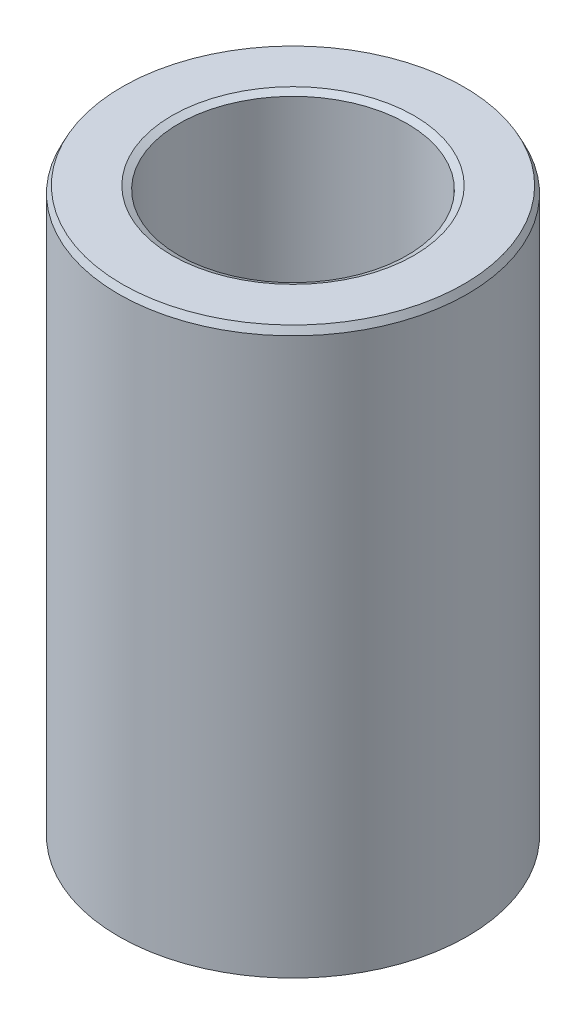
SolidWorks part; units mm, degrees
ref_plane "Front Plane" through (0, 0, 0) normal (0, 0, 1) x (1, 0, 0)
ref_plane "Top Plane" through (0, 0, 0) normal (0, 1, 0) x (1, 0, 0)
ref_plane "Right Plane" through (0, 0, 0) normal (1, 0, 0) x (0, 0, -1)
sketch "Sketch1" plane through (0, 0, 0) normal (0, 1, 0) x (1, 0, 0)
  circle A0 centre (0, 0) radius 27.5
  dimension "SLEEVE_OD" = 55
extrude "Boss-Extrude1" add sketch "Sketch1" along normal blind 89.3774
sketch "Sketch2" plane through (0, 0, 0) normal (0, 1, 0) x (1, 0, 0)
  circle A0 centre (0, 0) radius 18.0041
  dimension "BORE_D" = 36.0081
extrude "Cut-Extrude1" cut sketch "Sketch2" along normal through all
chamfer "Chamfer1" distance 1.0919 angle 26.585 4 edges at (0, 89.3774, 18.0041) (0, 0, 18.0041) (0, 0, 27.5) (0, 89.3774, 27.5) first distance on face at (0, 89.3774, 18.0041) first distance on face at (0, 0, 18.0041) first distance on face at (0, 89.3774, 27.5)
